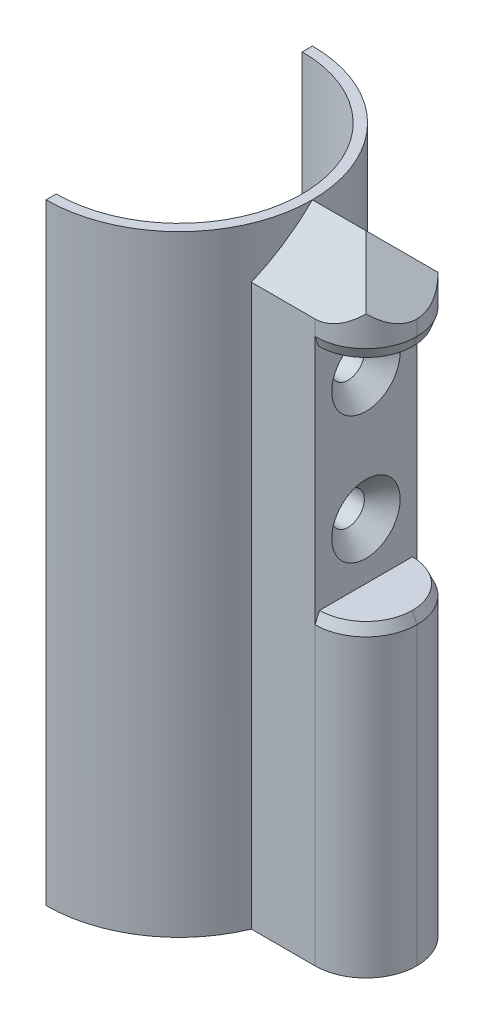
SolidWorks part; units mm, degrees
material "AISI 316 Arkusz stali nierdzewnej (SS)"
ref_plane "Płaszczyzna przednia" through (0, 0, 0) normal (0, 0, 1) x (1, 0, 0)
ref_plane "Płaszczyzna górna" through (0, 0, 0) normal (0, 1, 0) x (1, 0, 0)
ref_plane "Płaszczyzna prawa" through (0, 0, 0) normal (1, 0, 0) x (0, 0, -1)
sketch "Szkic2" plane through (0, 0, 0) normal (0, 1, 0) x (1, 0, 0)
  line L0 (24.1624, 10) -> (46.6624, 10)
  line L1 (24.1624, -10) -> (46.6624, -10)
  line L2 (46.6624, 10) -> (46.6624, -10)
  line L3 (0, 13.3006) -> (0, -13.3006) construction
  line L4 (0, 26.15) -> (0, 24.15)
  line L5 (0, -24.15) -> (0, -26.15)
  arc A0 (24.1624, -10) -> (0, -26.15) centre (0, 0) cw
  arc A1 (24.1624, 10) -> (0, 26.15) centre (0, 0) ccw
  arc A2 (0, 24.15) -> (0, -24.15) centre (0, 0) cw
  point P11 (0, 0)
  dimension "D1" = 26.15
  dimension "D7" = 24.15
  dimension "D2" = 20
  dimension "D3" = 10
  dimension "D4" = 26.15
  dimension "D5" = 22.5
  dimension "D6" = 26.15
  dimension "D8" = 24.15
  dimension "D9" = 24.15
extrude "Dodanie-wyciągnięcie1" add sketch "Szkic2" along normal blind 100 and the other way blind 20
chamfer "Sfazowanie1" distance 10 angle 45 3 edges at (35.4124, 100, -10) (46.6624, 100, 0) (35.4124, 100, 10)
fillet "Zaokrąglenie1" radius 10 2 edges at (46.6624, 35, -10) (46.6624, 35, 10)
ref_plane "Płaszczyzna1" through (36.66, 0, 0) normal (1, 0, 0) x (0, 0, -1)
sketch "Szkic3" plane through (36.66, 0, 0) normal (1, 0, 0) x (0, 0, -1)
  line L0 (-10, 85) -> (10, 85)
  line L1 (-10, 90) -> (-10, -20) construction
  line L2 (10, 90) -> (10, -20) construction
  line L3 (10, 85) -> (10, 40)
  line L4 (10, 40) -> (-10, 40)
  line L5 (-10, 40) -> (-10, 85)
  point P6 (0, 0)
  point P14 (0, 0)
  point P22 (0, 0)
  dimension "D5" = 5
  dimension "D1" = 20
  dimension "D2" = 20
  dimension "D3" = 45
extrude "Wytnij-wyciągnięcie1" cut sketch "Szkic3" along normal blind 100 contours L5 L0 L3 L4
chamfer "Sfazowanie2" distance 2 angle 24 4 edges at (36.6612, 40, -10) (36.6612, 40, 10) (43.7335, 40, -7.0711) (43.7335, 40, 7.0711) first distance on face at (33.5368, 48.75, -10) first distance on face at (33.5368, 48.75, 10) first distance on face at (42.698, 10, -6.0355) first distance on face at (42.698, 10, 6.0355)
chamfer "Sfazowanie3" distance 2 angle 20 4 edges at (36.6612, 85, 10) (36.6612, 85, -10) (43.7335, 85, 7.0711) (43.7335, 85, -7.0711) first distance on face at (33.5368, 48.25, 10) first distance on face at (33.5368, 48.25, -10) first distance on face at (42.6898, 88.3045, 6.0273) first distance on face at (42.6898, 88.3045, -6.0273)
sketch "Szkic5" plane through (36.66, 0, 0) normal (1, 0, 0) x (0, 0, -1)
  line L0 (-10, 85) -> (10, 85)
  line L1 (10, 85) -> (10, 40)
  line L2 (10, 40) -> (-10, 40)
  line L3 (-10, 40) -> (-10, 85)
  line L4 (-10, 76) -> (10, 76) construction
  line L5 (0, 85) -> (0, 40) construction
  line L6 (-10, 51) -> (10, 51) construction
  point P14 (0, 76)
  point P17 (0, 51)
  dimension "D1" = 9
  dimension "D2" = 25
  dimension "D3" = 11
hole_wizard "Pogłębienie stożkowe pod M6 Wkręt z łbem stożkowym płaskim2" positions "Szkic5" profile "Szkic6" countersink size "M6" standard "ISO"
sketch "Szkic6" plane through (36.66, 51, 0) normal (0, 1, 0) x (0, 0, -1)
  line L0 (0, 0) -> (0, 41.9228)
  line L1 (0, 41.9228) -> (3.2, 40)
  line L2 (3.2, 40) -> (3.2, 3.52)
  line L3 (3.2, 3.52) -> (6.72, 0)
  line L5 (6.72, 0) -> (0, 0)
  line L6 (-3.2, 3.52) -> (-6.72, 0) construction
  line L10 (0, 41.9228) -> (-3.2, 40) construction
  line L11 (0, -6.35) -> (0, 107.95) construction
  dimension "Średnica otworu" = 6.4
  dimension "Głębokośc otworu" = 40
  dimension "Średnica zewnętrznego pogłębienia stożkowego" = 13.44
  dimension "Kąt zewnętrznego pogłębienia stożkowego" = 90
  dimension "Kąt wiertła" = 118
sketch "Szkic7" plane through (0, -20, 0) normal (0, -1, 0) x (1, 0, 0)
  line L0 (36.6624, -10) -> (24.1624, -10) construction
  circle A0 centre (37, 0) radius 5
  arc A1 (0, -24.15) -> (0, 24.15) centre (0, 0) ccw construction
  point P2 (33.7217, 0)
  point P3 (32.3977, 0)
  point P4 (30.7064, 0)
  point P5 (30.6088, 0.5511)
  point P6 (30.3701, 0)
  point P11 (30.5, 0)
  dimension "D1" = 10
  dimension "D2" = 37
  dimension "D3" = 10
extrude "Wytnij-wyciągnięcie2" cut sketch "Szkic7" against normal blind 50 contours A0
